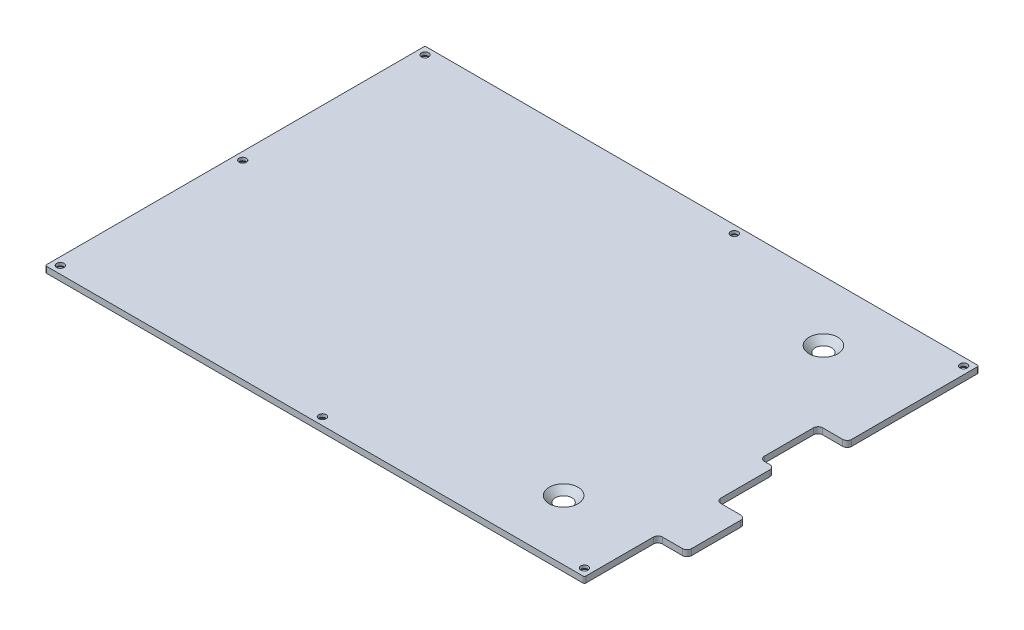
SolidWorks part; units mm, degrees
material "6061-T6 (SS)"
ref_plane "Front Plane" through (0, 0, 0) normal (0, 0, 1) x (1, 0, 0)
ref_plane "Top Plane" through (0, 0, 0) normal (0, 1, 0) x (1, 0, 0)
ref_plane "Right Plane" through (0, 0, 0) normal (1, 0, 0) x (0, 0, -1)
sketch "Sketch1" plane through (0, 0, 0) normal (0, 1, 0) x (1, 0, 0)
  line L0 (0, 0) -> (0, 124.3)
  line L1 (0, 124.3) -> (181.2125, 124.3)
  line L2 (181.2125, 124.3) -> (181.2125, 81.2)
  line L3 (181.2125, 81.2) -> (171.6875, 81.2)
  line L4 (171.6875, 81.2) -> (171.6875, 62.15)
  line L5 (171.6875, 62.15) -> (176.45, 62.15)
  line L6 (176.45, 62.15) -> (176.45, 43.1)
  line L7 (176.45, 43.1) -> (185.975, 43.1)
  line L8 (185.975, 43.1) -> (185.975, 24.05)
  line L9 (185.975, 24.05) -> (176.45, 24.05)
  line L10 (176.45, 24.05) -> (176.45, 0)
  line L11 (176.45, 0) -> (0, 0)
  dimension "D2" = 181.2125
  dimension "D3" = 43.1
  dimension "D4" = 4.7625
  dimension "D5" = 9.525
  dimension "D6" = 19.05
  dimension "D1" = 24.05
extrude "Plate Frame" add sketch "Sketch1" along normal blind 2
sketch "Sketch21" plane through (0, 0, 0) normal (0, -1, 0) x (-1, 0, 0)
  line L0 (-176.45, 0) -> (-176.45, 24.05) construction
  line L1 (-181.2125, 124.3) -> (0, 124.3) construction
  line L2 (-88.225, 2.5) -> (-2.5, 2.5) construction
  line L3 (-88.225, 2.5) -> (-173.95, 2.5) construction
  line L4 (0, 0) -> (-176.45, 0) construction
  line L5 (-2.5, 2.5) -> (-2.5, 62.15) construction
  line L6 (-2.5, 62.15) -> (-2.5, 121.8) construction
  line L7 (-2.5, 121.8) -> (-103.7125, 121.8) construction
  line L8 (-103.7125, 121.8) -> (-178.7125, 121.8) construction
  line L9 (-181.2125, 81.2) -> (-181.2125, 124.3) construction
  line L10 (0, 124.3) -> (0, 0) construction
  point P6 (-88.225, 2.5)
  point P7 (-173.95, 2.5)
  point P8 (-2.5, 2.5)
  point P9 (-2.5, 62.15)
  point P10 (-2.5, 121.8)
  point P11 (-103.7125, 121.8)
  point P12 (-178.7125, 121.8)
  dimension "D1" = 2.5
  dimension "D2" = 2.5
  dimension "D3" = 2.5
  dimension "D4" = 2.5
  dimension "D5" = 2.5
  dimension "D7" = 75
hole_wizard "CSK for M2 Flat Head Machine Screw2" positions "Sketch22" profile "Sketch23" countersink size "M2" standard "ANSI Metric" end condition through all
sketch "Sketch22" plane through (0, 0, 0) normal (0, -1, 0) x (-1, 0, 0)
  point P0 (-178.7125, 121.8)
  point P3 (-103.7125, 121.8)
  point P6 (-2.5, 121.8)
  point P9 (-2.5, 62.15)
  point P12 (-2.5, 2.5)
  point P15 (-88.225, 2.5)
  point P18 (-173.95, 2.5)
sketch "Sketch23" plane through (178.7125, 0, -121.8) normal (1, 0, 0) x (0, 0, -1)
  line L0 (0, 0) -> (0, 2)
  line L1 (0, 2) -> (1.2, 2)
  line L2 (1.2, 2) -> (1.2, 1)
  line L3 (1.2, 1) -> (2.2, 0)
  line L5 (2.2, 0) -> (0, 0)
  line L6 (-1.2, 1) -> (-2.2, 0) construction
  line L11 (0, -6.35) -> (0, 107.95) construction
  dimension "Thru Hole Dia." = 2.4
  dimension "Thru Hole Depth" = 2
  dimension "Near C'Sink Dia." = 4.4
  dimension "Near C'Sink Angle" = 90
sketch "Sketch24" plane through (0, 2, 0) normal (0, 1, 0) x (1, 0, 0)
  line L0 (2.5, 62.15) -> (150, 62.15) construction
  line L1 (150, 104.65) -> (150, 19.65) construction
  line L2 (150, 104.65) -> (25, 104.65) construction
  line L3 (25, 104.65) -> (25, 62.15) construction
  line L4 (0, 124.3) -> (0, 0) construction
  point P5 (150, 62.15)
  dimension "D1" = 150
  dimension "D2" = 85
  dimension "D3" = 25
hole_wizard "CSK for M4 Flat Head Machine Screw1" positions "Sketch25" profile "Sketch26" countersink size "M4" standard "ANSI Metric" end condition through all
sketch "Sketch25" plane through (0, 2, 0) normal (0, 1, 0) x (1, 0, 0)
  point P0 (150, 104.65)
  point P3 (150, 19.65)
sketch "Sketch26" plane through (150, 2, -104.65) normal (1, 0, 0) x (0, 0, 1)
  line L0 (0, 0) -> (0, 2)
  line L1 (0, 2) -> (2.25, 2)
  line L2 (2.25, 2) -> (2.25, 2.45)
  line L3 (2.25, 2.45) -> (4.7, 0)
  line L5 (4.7, 0) -> (0, 0)
  line L6 (-2.25, 2.45) -> (-4.7, 0) construction
  line L11 (0, -6.35) -> (0, 107.95) construction
  dimension "Thru Hole Dia." = 4.5
  dimension "Thru Hole Depth" = 2
  dimension "Near C'Sink Dia." = 9.4
  dimension "Near C'Sink Angle" = 90
fillet "Fillet3" radius 1.5 8 edges at (171.6875, 1, -81.2) (181.2125, 1, -81.2) (176.45, 1, -62.15) (171.6875, 1, -62.15) (176.45, 1, -43.1) (185.975, 1, -43.1) (185.975, 1, -24.05) (176.45, 1, -24.05)
fillet "Fillet4" radius 0.5 4 edges at (181.2125, 1, -124.3) (0, 1, 0) (176.45, 1, 0) (0, 1, -124.3)
equation "\"D5@Sketch1\"=19.05/2"
equation "\"D4@Sketch1\"=19.05/4"
equation "\"D3@Sketch1\"=19.05*2 + 5"
equation "\"D1@Sketch1\"=19.05 + 5"
equation "\"D2@Sketch1\"=9.25*19.05 + 5"
